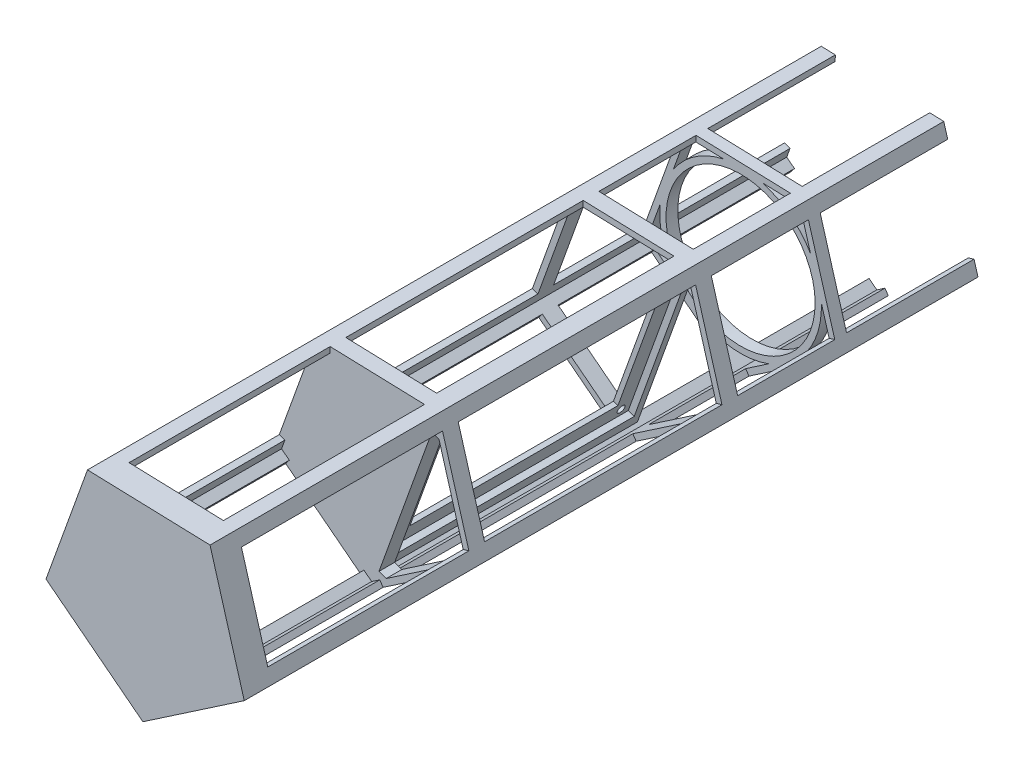
SolidWorks part; units mm, degrees
ref_plane "Front Plane" through (0, 0, 0) normal (0, 0, 1) x (1, 0, 0)
ref_plane "Top Plane" through (0, 0, 0) normal (0, 1, 0) x (1, 0, 0)
ref_plane "Right Plane" through (0, 0, 0) normal (1, 0, 0) x (0, 0, -1)
sketch "Sketch3" plane through (0, 0, 0) normal (0, 0, 1) x (1, 0, 0)
  line L0 (0, 0) -> (16.2851, 21.0012) construction
  line L1 (15.1489, 19.536) -> (-13.8986, 20.4445)
  line L2 (-13.8986, 20.4445) -> (-23.7387, -6.9006)
  line L3 (-23.7387, -6.9006) -> (-0.7728, -24.7093)
  line L4 (-0.7728, -24.7093) -> (23.2611, -8.3705)
  line L5 (0, 0) -> (29.9163, 0) construction
  line L6 (0, 0) -> (25.0057, -8.9983) construction
  line L10 (-0.8307, -26.5625) -> (25.0057, -8.9983)
  line L11 (25.0057, -8.9983) -> (16.2851, 21.0012)
  line L12 (16.2851, 21.0012) -> (-14.941, 21.9778)
  line L13 (-14.941, 21.9778) -> (-25.5191, -7.4182)
  line L14 (-25.5191, -7.4182) -> (-0.8307, -26.5625)
  line L15 (23.2611, -8.3705) -> (15.1489, 19.536)
  circle A0 centre (0, 0) radius 20 construction
  dimension "D2" = 40
extrude "Boss-Extrude2" add sketch "Sketch3" along normal blind 185
ref_plane "Plane1" through (0, 0, 92.5) normal (0, 0, 1) x (1, 0, 0)
sketch "Sketch4" plane through (0, 0, 0) normal (0, 0, -1) x (-1, 0, 0)
  line L0 (14.745, 18.0921) -> (16.1564, 18.6)
  line L1 (13.8986, 20.4445) -> (23.7387, -6.9006) construction
  line L2 (14.941, 21.9778) -> (25.5191, -7.4182) construction
  line L3 (24.3036, -4.0404) -> (22.8922, -4.5483)
  line L4 (22.8922, -4.5483) -> (14.745, 18.0921)
  line L5 (24.3036, -4.0404) -> (16.1564, 18.6)
  dimension "D1" = 2.5
  dimension "D2" = 2.5
extrude "Cut-Extrude1" cut sketch "Sketch4" against normal offset from surface (180 mm away) 5 up to face at (0, 0, 185)
ref_point "Point1"
ref_axis "Axis1" through (0, 0, 185) along (0, 0, 1)
pattern_circular "CirPattern1" count 5 over 360 about axis through (0, 0, 185) along (0, 0, 1) of "Cut-Extrude1"
ref_plane "Plane2" through (0, 0, 92.5) normal (0, 0, 1) x (1, 0, 0)
sketch "Sketch5" plane through (0, 0, 92.5) normal (0, 0, 1) x (1, 0, 0)
  line L0 (-2.0696, -25.6018) -> (14.7182, 21.0502) construction
  line L2 (-24.1133, -8.5083) -> (-1.8275, -25.7895) construction
  line L3 (23.2611, -8.3705) -> (0, 0) construction
  line L4 (-4.3961, -23.7977) -> (11.7756, 21.1422)
  line L8 (-2.0696, -25.6018) -> (-4.3961, -23.7977)
  line L10 (14.7182, 21.0502) -> (11.7756, 21.1422)
  line L11 (-2.0696, -25.6018) -> (14.7182, 21.0502)
  line L12 (-22.8004, 22.2236) -> (6.2471, 21.3151) construction
  dimension "D1" = 18
  dimension "D2" = 2.8
extrude "Boss-Extrude3" add sketch "Sketch5" along normal mid plane 64.5
sketch "Sketch6" plane through (0, 0, 124.75) normal (0, 0, 1) x (1, 0, 0)
  line L5 (-25.5191, -7.4182) -> (-0.8307, -26.5625)
  line L6 (-0.8307, -26.5625) -> (25.0057, -8.9983)
  line L7 (25.0057, -8.9983) -> (16.2851, 21.0012)
  line L8 (16.2851, 21.0012) -> (-14.941, 21.9778)
  line L9 (-14.941, 21.9778) -> (-25.5191, -7.4182)
  line L10 (-25.5191, -7.4182) -> (-0.8307, -26.5625)
  line L11 (-0.8307, -26.5625) -> (25.0057, -8.9983)
  line L12 (25.0057, -8.9983) -> (16.2851, 21.0012)
  line L13 (16.2851, 21.0012) -> (-14.941, 21.9778)
  line L14 (-14.941, 21.9778) -> (-25.5191, -7.4182)
  dimension "D1" = 0
extrude "Boss-Extrude4" add sketch "Sketch6" along normal blind 4
sketch "Sketch7" plane through (0, 0, 124.75) normal (0, 0, -1) x (-1, 0, 0)
  line L0 (-3.6897, -1.3278) -> (20.23, 7.2798) construction
  line L1 (-11.7756, 21.1422) -> (4.3961, -23.7977) construction
  line L2 (16.1564, 18.6) -> (24.3036, -4.0404) construction
  line L4 (19.0326, -2.4504) -> (13.1071, 14.0159)
  line L5 (0.2139, -9.2223) -> (-5.7115, 7.244)
  line L7 (19.0326, -2.4504) -> (-5.7115, 7.244) construction
  line L8 (0.2139, -9.2223) -> (13.1071, 14.0159) construction
  line L9 (9.6232, -5.8364) -> (3.6978, 10.63) construction
  line L11 (-11.7756, 21.1422) -> (4.3961, -23.7977) construction
  arc A0 (-5.7115, 7.244) -> (13.1071, 14.0159) centre (3.6978, 10.63) cw
  arc A1 (0.2139, -9.2223) -> (19.0326, -2.4504) centre (9.6232, -5.8364) ccw
  point P7 (6.6605, 2.3968)
  point P9 (13.0092, -15.2457)
  point P14 (0.3119, 20.0393)
  dimension "D1" = 37.5
  dimension "D2" = 20
  dimension "D3" = 1
extrude "Cut-Extrude2" cut sketch "Sketch7" against normal blind 2
sketch "Sketch8" plane through (6.3243, -2.2758, 0) normal (0.9409, -0.3386, 0) x (0, 0, -1)
  line L0 (-60.25, 0) -> (-124.75, 0) construction
  line L1 (-124.75, -23.2131) -> (-124.75, 23.2131) construction
  line L3 (-60.25, -23.2131) -> (-60.25, 23.2131) construction
  line L5 (-123, -20.5) -> (-123, 20.5)
  line L6 (-123, -20.5) -> (-62, -20.5)
  line L7 (-123, 20.5) -> (-62, 20.5)
  line L8 (-62, -20.5) -> (-62, 20.5)
  line L14 (-62, 20.5) -> (-123, -20.5) construction
  line L15 (-62, -20.5) -> (-123, 20.5) construction
  point P11 (-92.5, 0)
  point P14 (-92.5, 0)
  dimension "D1" = 61
  dimension "D2" = 41
extrude "Cut-Extrude3" cut sketch "Sketch8" against normal blind 1.6
sketch "Sketch9" plane through (4.8189, -1.7341, 0) normal (0.9409, -0.3386, 0) x (0, 0, -1)
  line L8 (-119, -16.5) -> (-66, -16.5)
  line L9 (-66, -16.5) -> (-66, 16.5)
  line L10 (-66, 16.5) -> (-119, 16.5)
  line L11 (-119, 16.5) -> (-119, -16.5)
  line L12 (-119, -16.5) -> (-66, -16.5)
  line L13 (-66, -16.5) -> (-66, 16.5)
  line L14 (-66, 16.5) -> (-119, 16.5)
  line L15 (-119, 16.5) -> (-119, -16.5)
  dimension "D1" = 4
extrude "Cut-Extrude4" cut sketch "Sketch9" against normal up to surface (1.2 mm away) up to face at (3.6897, -1.3278, 92.5)
sketch "Sketch10" plane through (0, 0, 60.25) normal (0, 0, -1) x (-1, 0, 0)
  line L25 (-23.2611, -8.3705) -> (0.7728, -24.7093)
  line L26 (0.7728, -24.7093) -> (23.7387, -6.9006)
  line L27 (23.7387, -6.9006) -> (13.8986, 20.4445)
  line L28 (13.8986, 20.4445) -> (-15.1489, 19.536)
  line L29 (-15.1489, 19.536) -> (-23.2611, -8.3705)
  line L30 (0.8307, -26.5625) -> (25.5191, -7.4182)
  line L31 (-25.0057, -8.9983) -> (0.8307, -26.5625)
  line L32 (-16.2851, 21.0012) -> (-25.0057, -8.9983)
  line L33 (14.941, 21.9778) -> (-16.2851, 21.0012)
  line L34 (25.5191, -7.4182) -> (14.941, 21.9778)
  line L40 (0.8307, -26.5625) -> (25.5191, -7.4182)
  line L41 (-25.0057, -8.9983) -> (0.8307, -26.5625)
  line L42 (-16.2851, 21.0012) -> (-25.0057, -8.9983)
  line L43 (14.941, 21.9778) -> (-16.2851, 21.0012)
  line L44 (25.5191, -7.4182) -> (14.941, 21.9778)
  dimension "D1" = 0
extrude "Boss-Extrude5" add sketch "Sketch10" against normal blind 4
sketch "Sketch11" plane through (0, 0, 60.25) normal (0, 0, -1) x (-1, 0, 0)
  line L0 (3.8621, -22.3137) -> (4.3961, -23.7977)
  line L1 (4.3961, -23.7977) -> (3.6676, -24.3627)
  line L2 (-11.2416, 19.6582) -> (-11.7756, 21.1422)
  line L3 (-11.7756, 21.1422) -> (-12.697, 21.1134)
  line L4 (21.7631, -8.4326) -> (3.8621, -22.3137)
  line L7 (3.8621, -22.3137) -> (-11.2416, 19.6582)
  line L9 (-14.1842, 19.5662) -> (1.5355, -24.1178)
  line L10 (-14.1842, 19.5662) -> (1.5355, -24.1178)
  line L11 (-12.697, 21.1134) -> (11.3529, 21.8656) construction
  line L13 (3.8621, -22.3137) -> (-11.2416, 19.6582) construction
  line L18 (22.6823, -9.618) -> (3.6676, -24.3627) construction
  line L19 (3.8621, -22.3137) -> (-11.2416, 19.6582)
  line L27 (-11.2416, 19.6582) -> (11.3998, 20.3663)
  line L31 (1.5355, -24.1178) -> (2.7484, -23.1773)
  line L33 (1.5355, -24.1178) -> (2.7484, -23.1773)
  line L35 (2.7484, -23.1773) -> (3.6676, -24.3627)
  line L37 (2.7484, -23.1773) -> (3.6676, -24.3627)
  line L39 (3.6676, -24.3627) -> (22.6823, -9.618)
  line L41 (22.6823, -9.618) -> (21.7631, -8.4326)
  line L43 (11.3998, 20.3663) -> (11.3529, 21.8656)
  line L45 (11.3529, 21.8656) -> (-12.697, 21.1134)
  line L47 (-12.697, 21.1134) -> (-12.6502, 19.6141)
  line L48 (-12.697, 21.1134) -> (-12.6502, 19.6141)
  line L49 (-12.6502, 19.6141) -> (-14.1842, 19.5662)
  line L50 (-12.6502, 19.6141) -> (-14.1842, 19.5662)
  dimension "D1" = 0
ref_plane "Plane3" through (0, 0, 32.5) normal (0, 0, 1) x (1, 0, 0)
sketch "Sketch14" plane through (0, 0, 32.5) normal (0, 0, 1) x (1, 0, 0)
  line L5 (-25.5191, -7.4182) -> (-0.8307, -26.5625)
  line L6 (-0.8307, -26.5625) -> (25.0057, -8.9983)
  line L7 (25.0057, -8.9983) -> (16.2851, 21.0012)
  line L8 (16.2851, 21.0012) -> (-14.941, 21.9778)
  line L9 (-14.941, 21.9778) -> (-25.5191, -7.4182)
  line L11 (-0.8307, -26.5625) -> (25.0057, -8.9983)
  line L12 (25.0057, -8.9983) -> (16.2851, 21.0012)
  line L16 (23.2611, -8.3705) -> (15.3259, -13.7651)
  line L18 (-0.7728, -24.7093) -> (-8.3554, -18.8294)
  line L20 (-23.7387, -6.9006) -> (-20.4898, 2.1279)
  line L22 (-13.8986, 20.4445) -> (-4.308, 20.1445)
  line L24 (15.1489, 19.536) -> (17.8273, 10.3221)
  line L25 (7.1625, -19.3147) -> (-0.7728, -24.7093)
  line L26 (20.5827, 0.8433) -> (23.2611, -8.3705)
  line L27 (5.5584, 19.8359) -> (15.1489, 19.536)
  line L28 (-17.1475, 11.416) -> (-13.8986, 20.4445)
  line L29 (-16.1561, -12.7805) -> (-23.7387, -6.9006)
  line L30 (16.2851, 21.0012) -> (-14.941, 21.9778)
  line L31 (-14.941, 21.9778) -> (-25.5191, -7.4182)
  line L32 (-25.5191, -7.4182) -> (-0.8307, -26.5625)
  circle A3 centre (0, 0) radius 19
  arc A8 (15.3259, -13.7651) -> (20.5827, 0.8433) centre (0, 0) ccw
  circle A9 centre (0, 0) radius 20.6 construction
  arc A10 (17.8273, 10.3221) -> (5.5584, 19.8359) centre (0, 0) ccw
  arc A11 (-4.308, 20.1445) -> (-17.1475, 11.416) centre (0, 0) ccw
  arc A12 (-20.4898, 2.1279) -> (-16.1561, -12.7805) centre (0, 0) ccw
  arc A13 (-8.3554, -18.8294) -> (7.1625, -19.3147) centre (0, 0) ccw
  dimension "D2" = 38
  dimension "D1" = 0
  dimension "D3" = 1.6
extrude "Boss-Extrude8" add sketch "Sketch14" along normal blind 3
ref_plane "Plane4" through (0, 0, 29.5) normal (0, 0, -1) x (-1, 0, 0)
sketch "Sketch15" plane through (0, 0, 29.5) normal (0, 0, -1) x (-1, 0, 0)
  line L0 (-23.2611, -8.3705) -> (0.7728, -24.7093)
  line L1 (0.7728, -24.7093) -> (23.7387, -6.9006)
  line L2 (23.7387, -6.9006) -> (13.8986, 20.4445)
  line L3 (13.8986, 20.4445) -> (-15.1489, 19.536)
  line L4 (-15.1489, 19.536) -> (-23.2611, -8.3705)
  line L5 (0.8307, -26.5625) -> (25.5191, -7.4182)
  line L6 (-25.0057, -8.9983) -> (0.8307, -26.5625)
  line L7 (-16.2851, 21.0012) -> (-25.0057, -8.9983)
  line L8 (14.941, 21.9778) -> (-16.2851, 21.0012)
  line L9 (25.5191, -7.4182) -> (14.941, 21.9778)
  line L10 (0.8307, -26.5625) -> (25.5191, -7.4182)
  line L11 (-25.0057, -8.9983) -> (0.8307, -26.5625)
  line L12 (-16.2851, 21.0012) -> (-25.0057, -8.9983)
  line L13 (14.941, 21.9778) -> (-16.2851, 21.0012)
  line L14 (25.5191, -7.4182) -> (14.941, 21.9778)
  dimension "D1" = 0
sketch "Sketch29" plane through (0, 0, 185) normal (0, 0, 1) x (1, 0, 0)
  line L5 (-25.5191, -7.4182) -> (-0.8307, -26.5625)
  line L6 (-0.8307, -26.5625) -> (25.0057, -8.9983)
  line L7 (25.0057, -8.9983) -> (16.2851, 21.0012)
  line L8 (16.2851, 21.0012) -> (-14.941, 21.9778)
  line L9 (-14.941, 21.9778) -> (-25.5191, -7.4182)
  line L10 (-25.5191, -7.4182) -> (-0.8307, -26.5625)
  line L11 (-0.8307, -26.5625) -> (25.0057, -8.9983)
  line L12 (25.0057, -8.9983) -> (16.2851, 21.0012)
  line L13 (16.2851, 21.0012) -> (-14.941, 21.9778)
  line L14 (-14.941, 21.9778) -> (-25.5191, -7.4182)
  dimension "D1" = 0
extrude "Boss-Extrude13" add sketch "Sketch29" along normal blind 2
sketch "Sketch30" plane through (0, 0, 187) normal (0, 0, 1) x (1, 0, 0)
  line L0 (25.0057, -8.9983) -> (-20.23, 7.2798) construction
  line L1 (-14.941, 21.9778) -> (-25.5191, -7.4182) construction
  line L2 (3.1542, -17.0767) -> (-13.3121, -11.1513)
  line L3 (18.5086, -9.8487) -> (20.5401, -4.2031)
  line L4 (-20.5401, 4.2031) -> (-18.5086, 9.8487)
  line L5 (13.3121, 11.1513) -> (-3.1542, 17.0767)
  line L6 (14.4454, -21.1398) -> (-14.4454, 21.1398) construction
  line L7 (-24.6033, -7.0881) -> (24.6033, 7.0881) construction
  line L8 (19.5243, -7.0259) -> (-19.5243, 7.0259) construction
  arc A0 (18.5086, -9.8487) -> (3.1542, -17.0767) centre (7.2174, -5.7855) cw
  arc A1 (-18.5086, 9.8487) -> (-3.1542, 17.0767) centre (-7.2174, 5.7855) cw
  arc A2 (-13.3121, -11.1513) -> (-20.5401, 4.2031) centre (-9.2489, 0.1399) cw
  arc A3 (20.5401, -4.2031) -> (13.3121, 11.1513) centre (9.2489, -0.1399) ccw
  point P5 (0, 0)
  dimension "D3" = 12
  dimension "D1" = 30
  dimension "D2" = 41.5
extrude "Cut-Extrude8" [suppressed] cut sketch "Sketch30" against normal blind 0.6
sketch "Sketch31" [suppressed] plane through (0, 0, 186.4) normal (0, 0, 1) x (1, 0, 0)
  line L0 (25.0057, -8.9983) -> (0, 0) construction
  line L1 (12.0432, 0.9801) -> (8.6573, -8.4292)
  line L2 (12.0432, 0.9801) -> (-8.6573, 8.4292)
  line L3 (8.6573, -8.4292) -> (-12.0432, -0.9801)
  line L4 (-8.6573, 8.4292) -> (-12.0432, -0.9801)
  line L5 (12.0432, 0.9801) -> (-12.0432, -0.9801) construction
  line L6 (8.6573, -8.4292) -> (-8.6573, 8.4292) construction
  line L7 (-10.3503, 3.7246) -> (10.3503, -3.7246) construction
  dimension "D1" = 22
  dimension "D2" = 10
extrude "Cut-Extrude9" [suppressed] cut sketch "Sketch31" against normal up to surface (1.4 mm away) up to face at (0, 0, 185)
sketch "Sketch32" [suppressed] plane through (0, 0, 187) normal (0, 0, 1) x (1, 0, 0)
  line L0 (0, 0) -> (-36.3954, 13.0969) construction
  line L1 (-22.7695, 0.2228) -> (-21.2398, -0.3276)
  line L3 (-14.941, 21.9778) -> (-25.5191, -7.4182) construction
  line L4 (-17.6906, 14.3368) -> (-16.1609, 13.7863)
  line L5 (-18.5086, 9.8487) -> (-20.5401, 4.2031) construction
  line L6 (-18.5086, 9.8487) -> (-20.5401, 4.2031)
  line L7 (-17.6906, 14.3368) -> (-22.7695, 0.2228)
  arc A0 (-20.5401, 4.2031) -> (-13.3121, -11.1513) centre (-9.2489, 0.1399) ccw construction
  arc A1 (-20.5401, 4.2031) -> (-13.3121, -11.1513) centre (-9.2489, 0.1399) ccw construction
  arc A3 (-3.1542, 17.0767) -> (-18.5086, 9.8487) centre (-7.2174, 5.7855) ccw construction
  arc A4 (-16.1609, 13.7863) -> (-18.5086, 9.8487) centre (-7.2174, 5.7855) ccw
  arc A5 (-20.5401, 4.2031) -> (-21.2398, -0.3276) centre (-9.2489, 0.1399) ccw
  dimension "D1" = 7.5
extrude "Cut-Extrude11" [suppressed] cut sketch "Sketch32" against normal up to surface (0.6 mm away) up to face at (-13.7489, 20.2244, 0)
sketch "Sketch34" [suppressed] plane through (0, 0, 186.4) normal (0, 0, 1) x (1, 0, 0)
  line L0 (-22.7695, 0.2228) -> (-17.6906, 14.3368)
  line L1 (-22.7695, 0.2228) -> (-22.0638, -0.0311)
  line L2 (-17.6906, 14.3368) -> (-16.9849, 14.0828)
  line L3 (-22.0638, -0.0311) -> (-16.9849, 14.0828)
  line L4 (-13.3121, -11.1513) -> (3.1542, -17.0767)
  line L5 (18.5086, -9.8487) -> (20.5401, -4.2031)
  line L6 (13.3121, 11.1513) -> (-3.1542, 17.0767)
  line L7 (-18.5086, 9.8487) -> (-20.5401, 4.2031)
  line L8 (-13.3121, -11.1513) -> (3.1542, -17.0767) construction
  line L9 (18.5086, -9.8487) -> (20.5401, -4.2031) construction
  line L10 (13.3121, 11.1513) -> (-3.1542, 17.0767) construction
  line L11 (-18.5086, 9.8487) -> (-20.5401, 4.2031) construction
  arc A4 (3.1542, -17.0767) -> (18.5086, -9.8487) centre (7.2174, -5.7855) ccw
  arc A5 (20.5401, -4.2031) -> (13.3121, 11.1513) centre (9.2489, -0.1399) ccw
  arc A6 (-3.1542, 17.0767) -> (-18.5086, 9.8487) centre (-7.2174, 5.7855) ccw
  arc A7 (-20.5401, 4.2031) -> (-13.3121, -11.1513) centre (-9.2489, 0.1399) ccw
  arc A8 (3.1542, -17.0767) -> (18.5086, -9.8487) centre (7.2174, -5.7855) ccw construction
  arc A9 (20.5401, -4.2031) -> (13.3121, 11.1513) centre (9.2489, -0.1399) ccw construction
  arc A10 (-3.1542, 17.0767) -> (-18.5086, 9.8487) centre (-7.2174, 5.7855) ccw construction
  arc A11 (-20.5401, 4.2031) -> (-13.3121, -11.1513) centre (-9.2489, 0.1399) ccw construction
  dimension "D1" = 0
sketch "Sketch38" plane through (0, 0, 124.75) normal (0, 0, -1) x (-1, 0, 0)
  line L5 (13.8986, 20.4445) -> (-15.1489, 19.536)
  line L6 (-15.1489, 19.536) -> (-23.2611, -8.3705)
  line L7 (-23.2611, -8.3705) -> (0.7728, -24.7093)
  line L8 (0.7728, -24.7093) -> (23.7387, -6.9006)
  line L9 (23.7387, -6.9006) -> (13.8986, 20.4445)
  line L11 (-16.3988, 15.2363) -> (-23.2611, -8.3705)
  line L12 (-23.2611, -8.3705) -> (-2.9303, -22.1919)
  line L16 (-1.0956, -21.5316) -> (-2.9303, -22.1919)
  line L17 (0.03, -24.6596) -> (-15.6897, 19.0244)
  line L18 (-1.0956, -21.5316) -> (-14.5641, 15.8965)
  line L19 (-14.5641, 15.8965) -> (-16.3988, 15.2363)
  dimension "D3" = 1.6
  dimension "D4" = 1.6
  dimension "D1" = 0
  dimension "D2" = 1.6
extrude "Cut-Extrude14" cut sketch "Sketch38" against normal up to surface (4 mm away) up to face at (0, 0, 128.75)
sketch "Sketch40" plane through (-18.8186, 6.7719, 0) normal (0.9409, -0.3386, 0) x (0, 0, -1)
  line L0 (-185, 14.5309) -> (-185, -14.5309) construction
  line L1 (-185, 7.5) -> (-183.5, 7.5)
  line L2 (-185, 7.5) -> (-185, -7.5)
  line L3 (-185, -7.5) -> (-183.5, -7.5)
  line L4 (-183.5, 7.5) -> (-183.5, -7.5)
  line L5 (-183.5, 0) -> (-185, 0) construction
  point P9 (-185, 0)
  dimension "D1" = 15
  dimension "D2" = 1.5
ref_plane "Plane5" through (14.5641, 15.8965, 124.75) normal (0.3386, 0.9409, 0) x (0.9409, -0.3386, 0)
sketch "Sketch42" plane through (0, 0, 128.75) normal (0, 0, 1) x (1, 0, 0)
  line L0 (-20.23, 7.2798) -> (0, 0) construction
  line L1 (-16.1564, 18.6) -> (-24.3036, -4.0404) construction
  line L2 (5.4365, -16.774) -> (-14.8782, -9.4637) construction
  line L3 (5.4365, -16.774) -> (14.8782, 9.4637) construction
  line L4 (-14.8782, -9.4637) -> (-5.4365, 16.774) construction
  line L5 (14.8782, 9.4637) -> (-5.4365, 16.774) construction
  line L6 (5.4365, -16.774) -> (-5.4365, 16.774) construction
  line L7 (-14.8782, -9.4637) -> (14.8782, 9.4637) construction
  line L8 (-3.9066, 13.524) -> (11.6282, 7.9338) construction
  line L9 (4.7208, 13.1189) -> (-4.7208, -13.1189) construction
  line L10 (2.2472, -13.2032) -> (-10.1449, -8.7439) construction
  line L11 (-1.5355, -24.1178) -> (14.1842, 19.5662) construction
  line L12 (-1.5355, -24.1178) -> (14.1842, 19.5662)
  line L13 (12.891, 3.9416) -> (6.1392, -14.8212) construction
  line L14 (12.891, 3.9416) -> (10.6328, 4.7542) construction
  line L15 (6.1392, -14.8212) -> (3.881, -14.0086) construction
  line L16 (10.6328, 4.7542) -> (3.881, -14.0086) construction
  circle A0 centre (11.6282, 7.9338) radius 1
  circle A1 centre (-3.9066, 13.524) radius 1
  circle A2 centre (2.2472, -13.2032) radius 1
  circle A3 centre (-10.1449, -8.7439) radius 1
  point P1 (3.8608, 10.7289)
  point P2 (0, 0)
  point P19 (-3.9488, -10.9735)
  dimension "D4" = 2
  dimension "D7" = 2
  dimension "D1" = 21.59
  dimension "D2" = 27.8848
  dimension "D3" = 16.51
  dimension "D5" = 2.54
  dimension "D6" = 13.17
  dimension "D8" = 2.28
  dimension "D9" = 2.4
sketch "Sketch43" plane through (0, 0, 128.75) normal (0, 0, 1) x (1, 0, 0)
  line L1 (10.8306, 5.5214) -> (12.5507, 10.3013)
  line L2 (12.891, 3.9416) -> (10.6328, 4.7542) construction
  line L3 (12.891, 3.9416) -> (10.6328, 4.7542)
  line L4 (1.0956, -21.5316) -> (14.5641, 15.8965) construction
  arc A0 (12.5507, 10.3013) -> (10.8306, 5.5214) centre (11.6282, 7.9338) cw
  point P4 (12.5507, 10.3013)
  line M27 (1.0956, -21.5316) -> (14.5641, 15.8965)
  dimension "D1" = 2.5409
extrude "Boss-Extrude15" [suppressed] add sketch "Sketch43" against normal up to surface (4 mm away) contours A0 M27 up to face at (11.7736, -4.2367, 124.75)
sketch "Sketch44" plane through (0, 0, 128.75) normal (0, 0, 1) x (1, 0, 0)
  circle A0 centre (-10.1449, -8.7439) radius 1 construction
  circle A1 centre (-3.9066, 13.524) radius 1 construction
  circle A2 centre (-10.1449, -8.7439) radius 1
  circle A3 centre (-3.9066, 13.524) radius 1
extrude "Cut-Extrude18" [suppressed] cut sketch "Sketch42" against normal blind 3.5 contours A0 | A2
extrude "Cut-Extrude19" [suppressed] cut sketch "Sketch44" against normal blind 1.5
sketch "Sketch45" plane through (0, 0, 128.75) normal (0, 0, 1) x (1, 0, 0)
  line L0 (-1.8971, -16.8531) -> (9.2766, 14.1976) construction
  line L1 (-1.8971, -16.8531) -> (10.6309, 17.9614) construction
  line L2 (13.2655, 17.0133) -> (-0.6169, -21.5649) construction
  line L3 (13.2655, 17.0133) -> (-0.6169, -21.5649) construction
  line L4 (-4.3961, -23.7977) -> (11.7756, 21.1422)
  line L5 (11.7756, 21.1422) -> (14.7182, 21.0502)
  line L6 (14.7182, 21.0502) -> (-2.0696, -25.6018)
  line L7 (-2.0696, -25.6018) -> (-4.3961, -23.7977)
  line L8 (-22.6823, -9.618) -> (-3.6676, -24.3627) construction
  line L11 (12.697, 21.1134) -> (-11.3529, 21.8656) construction
sketch "Sketch46" plane through (0, 0, 128.75) normal (0, 0, 1) x (1, 0, 0)
  line L0 (-8.1098, 21.7641) -> (-20.1403, -11.5891)
  line L1 (-8.1098, 21.7641) -> (-4.6098, 21.6547)
  line L2 (-20.1403, -11.5891) -> (-17.3745, -13.7339)
  line L3 (-4.6098, 21.6547) -> (-17.3745, -13.7339)
  line L4 (-16.1564, 18.6) -> (-24.3036, -4.0404) construction
  line L5 (-1.5355, -24.1178) -> (14.1842, 19.5662) construction
  line L6 (-1.5355, -24.1178) -> (14.1842, 19.5662)
  line L8 (12.697, 21.1134) -> (-11.3529, 21.8656) construction
  line L9 (-22.6823, -9.618) -> (-3.6676, -24.3627) construction
  dimension "D1" = 3.5
  dimension "D2" = 3.5
  dimension "D3" = 6.5
sketch "Sketch49" plane through (0, 0, 126.75) normal (0, 0, -1) x (-1, 0, 0)
  line L0 (-2.7488, -0.9892) -> (16.0698, 5.7828) construction
  line L1 (-5.7115, 7.244) -> (0.2139, -9.2223) construction
  line L2 (19.0326, -2.4504) -> (13.1071, 14.0159) construction
  line L3 (12.4006, 7.1193) -> (14.0935, 2.4146) construction
  line L4 (15.2234, 8.1351) -> (16.9163, 3.4304)
  line L5 (9.5778, 6.1035) -> (11.2707, 1.3988)
  arc A0 (15.2234, 8.1351) -> (9.5778, 6.1035) centre (12.4006, 7.1193) ccw
  arc A1 (11.2707, 1.3988) -> (16.9163, 3.4304) centre (14.0935, 2.4146) ccw
  point P8 (13.247, 4.767)
  dimension "D1" = 6
  dimension "D2" = 5
sketch "Sketch54" plane through (4.8189, -1.7341, 0) normal (0.9409, -0.3386, 0) x (0, 0, -1)
  line L0 (-62, 20.5) -> (-123, 20.5) construction
  line L1 (-123, 20.5) -> (-123, -20.5) construction
  line L2 (-66, 0) -> (-119, 0) construction
  line L3 (-66, -16.5) -> (-66, 16.5) construction
  line L4 (-119, 16.5) -> (-119, -16.5) construction
  line L5 (-92.5, 16.5) -> (-92.5, -16.5) construction
  line L6 (-66, 16.5) -> (-119, 16.5) construction
  line L7 (-119, -16.5) -> (-66, -16.5) construction
  circle A0 centre (-122, 19.5) radius 0.5
  circle A1 centre (-122, -19.5) radius 0.5
  circle A2 centre (-63, -19.5) radius 0.5
  circle A3 centre (-63, 19.5) radius 0.5
  dimension "D1" = 1
  dimension "D2" = 1
  dimension "D3" = 1
ref_plane "Plane8" through (15.2997, 42.5167, 0) normal (-0.3386, -0.9409, 0) x (-0.9409, 0.3386, 0)
sketch "Sketch61" plane through (4.8189, -1.7341, 0) normal (0.9409, -0.3386, 0) x (0, 0, -1)
  line L0 (-123, 20.5) -> (-123, -20.5) construction
  line L1 (-123, -20.5) -> (-62, -20.5) construction
  line L2 (-62, 0) -> (-123, 0) construction
  line L3 (-62, -20.5) -> (-62, 20.5) construction
  line L4 (-92.5, 20.5) -> (-92.5, -20.5) construction
  line L5 (-62, 20.5) -> (-123, 20.5) construction
  line L6 (-123, -20.5) -> (-62, -20.5) construction
  circle A0 centre (-120.5, -18.5) radius 1
  circle A1 centre (-64.5, -18.5) radius 1
  circle A2 centre (-120.5, 18.5) radius 1
  circle A3 centre (-64.5, 18.5) radius 1
  dimension "D3" = 2
  dimension "D1" = 2.5
  dimension "D2" = 2
extrude "Cut-Extrude22" cut sketch "Sketch61" against normal up to surface (1.2 mm away) up to face at (3.6897, -1.3278, 92.5)
